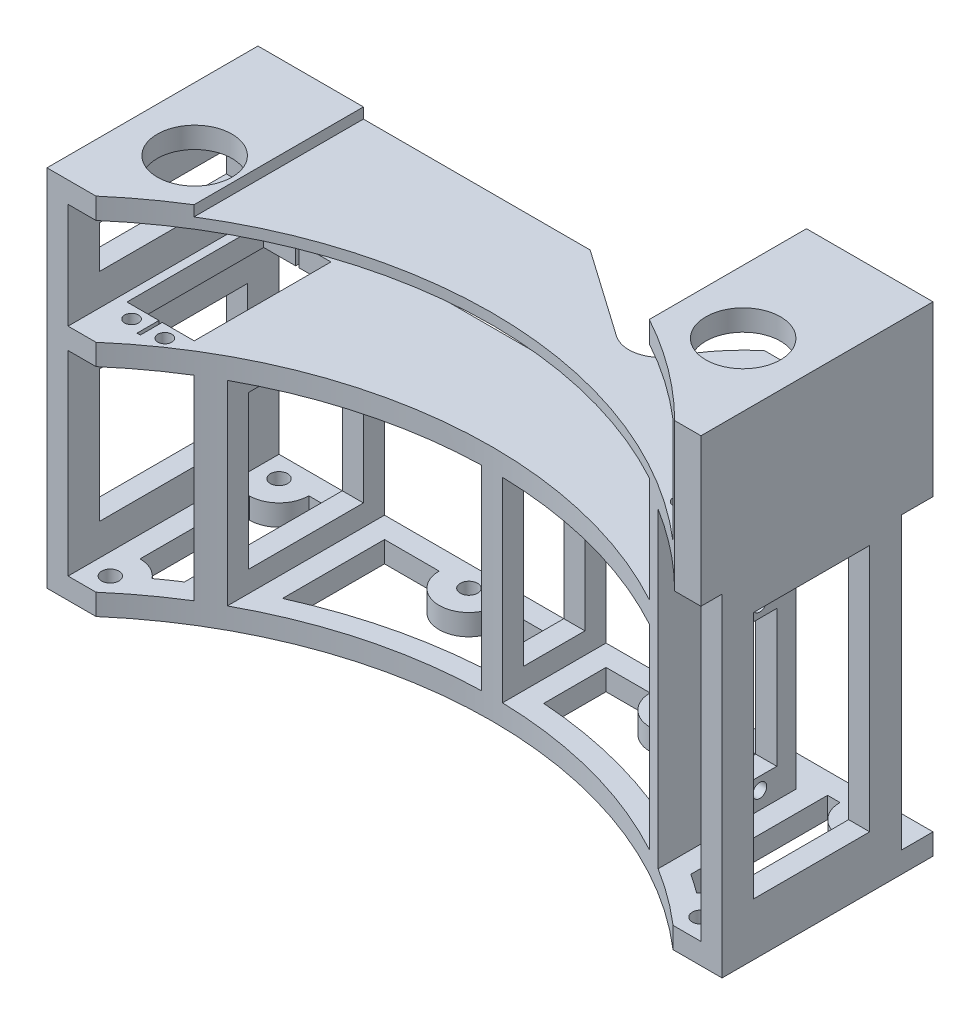
SolidWorks part; units mm, degrees
ref_plane "Front Plane" through (0, 0, 0) normal (0, 0, 1) x (1, 0, 0)
ref_plane "Top Plane" through (0, 0, 0) normal (0, 1, 0) x (1, 0, 0)
ref_plane "Right Plane" through (0, 0, 0) normal (1, 0, 0) x (0, 0, -1)
sketch "Sketch1" plane through (0, 0, 0) normal (0, 0, 1) x (1, 0, 0)
  line L0 (-101.6, 106.425) -> (101.6, 106.425)
  line L1 (-101.6, 0) -> (101.6, 0)
  line L2 (-101.6, 0) -> (-101.6, 106.425)
  line L4 (101.6, 0) -> (101.6, 106.425)
  point P5 (0, 0)
  dimension "D1" = 203.2
  dimension "D2" = 106.425
extrude "Boss-Extrude1" add sketch "Sketch1" along normal mid plane 63.5 contours L1 L4 L0 L2 | L0 region at (0, 53.2125, 0)
sketch "Sketch4" plane through (0, 0, -31.75) normal (0, 0, -1) x (-1, 0, 0)
  line L0 (-101.6, 0) -> (-101.6, 106.425) construction
  line L1 (101.6, 0) -> (101.6, 106.425) construction
  line L2 (-95.25, 103.25) -> (95.25, 103.25)
  line L3 (-95.25, 103.25) -> (-95.25, 71.5)
  line L4 (-95.25, 71.5) -> (95.25, 71.5)
  line L5 (95.25, 103.25) -> (95.25, 71.5)
  line L11 (-95.25, 65.15) -> (95.25, 65.15)
  line L12 (-95.25, 65.15) -> (-95.25, 6.35)
  line L13 (-95.25, 6.35) -> (95.25, 6.35)
  line L14 (95.25, 65.15) -> (95.25, 6.35)
  line L15 (101.6, 0) -> (-101.6, 0) construction
  dimension "D4" = 6.35
  dimension "D1" = 6.35
  dimension "D2" = 71.5
  dimension "D3" = 6.35
  dimension "D5" = 6.35
  dimension "D6" = 31.75
extrude "Cut-Extrude2" cut sketch "Sketch4" against normal through all
sketch "Sketch8" plane through (0, 0, 0) normal (0, 0, 1) x (1, 0, 0)
  line L0 (-95.25, 65.15) -> (95.25, 65.15) construction
  line L1 (-69.85, 65.15) -> (-63.5, 65.15)
  line L2 (-69.85, 65.15) -> (-69.85, 6.35)
  line L3 (-69.85, 6.35) -> (-63.5, 6.35)
  line L4 (-63.5, 65.15) -> (-63.5, 6.35)
  line L5 (95.25, 6.35) -> (-95.25, 6.35) construction
  line L6 (-95.25, 103.25) -> (95.25, 103.25) construction
  line L7 (63.5, 103.25) -> (69.85, 103.25)
  line L8 (63.5, 103.25) -> (63.5, 6.35)
  line L9 (63.5, 6.35) -> (69.85, 6.35)
  line L10 (69.85, 103.25) -> (69.85, 6.35)
  line L11 (95.25, 65.15) -> (95.25, 6.35) construction
  line L12 (-95.25, 6.35) -> (-95.25, 65.15) construction
  line L13 (-101.6, 0) -> (101.6, 0) construction
  line L14 (-3.175, 65.15) -> (3.175, 65.15)
  line L15 (-3.175, 65.15) -> (-3.175, 6.35)
  line L16 (-3.175, 6.35) -> (3.175, 6.35)
  line L17 (3.175, 65.15) -> (3.175, 6.35)
  point P24 (0, 0)
  point P25 (0, 6.35)
  dimension "D1" = 6.35
  dimension "D2" = 6.35
  dimension "D3" = 25.4
  dimension "D4" = 25.4
  dimension "D5" = 6.35
extrude "Boss-Extrude2" add sketch "Sketch8" along normal up to surface (31.75 mm away) from surface up to face at (0, 87.375, 31.75) starting at face at (0, 87.375, -31.75)
sketch "Sketch15" plane through (0, 103.25, 0) normal (0, -1, 0) x (1, 0, 0)
  line L4 (69.85, 31.75) -> (69.85, -31.75)
  line L5 (69.85, -31.75) -> (95.25, -31.75)
  line L6 (95.25, -31.75) -> (95.25, 31.75)
  line L7 (95.25, 31.75) -> (69.85, 31.75)
  line L8 (69.85, 31.75) -> (69.85, -31.75)
  line L9 (69.85, -31.75) -> (95.25, -31.75)
  line L10 (95.25, -31.75) -> (95.25, 31.75)
  line L11 (95.25, 31.75) -> (69.85, 31.75)
  dimension "D1" = 0
extrude "Boss-Extrude4" add sketch "Sketch15" along normal blind 3.175
sketch "Sketch2" plane through (0, 71.5, 0) normal (0, 1, 0) x (1, 0, 0)
  line L0 (-92.677, 24.55) -> (-72.423, -16.604) construction
  line L29 (-92.677, 24.55) -> (-83.05, 24.55)
  line L30 (-92.677, 24.55) -> (-92.677, -16.604)
  line L31 (-92.677, -16.604) -> (-83.05, -16.604)
  line L34 (-72.423, 24.55) -> (-72.423, -16.604)
  line L58 (69.85, 31.75) -> (69.85, -31.75)
  line L59 (69.85, -31.75) -> (95.25, -31.75)
  line L60 (95.25, -31.75) -> (95.25, 31.75)
  line L61 (95.25, 31.75) -> (69.85, 31.75)
  line L62 (69.85, 31.75) -> (69.85, -31.75)
  line L63 (69.85, -31.75) -> (95.25, -31.75)
  line L64 (95.25, -31.75) -> (95.25, 31.75)
  line L65 (95.25, 31.75) -> (69.85, 31.75)
  line L78 (-72.423, 24.55) -> (-92.677, -16.604) construction
  line L79 (-87.55, 28.273) -> (-77.55, -20.327) construction
  line L80 (-87.55, -20.327) -> (-77.55, 28.273) construction
  line L81 (-82.05, -16.604) -> (-72.423, -16.604)
  line L82 (-82.05, -16.604) -> (-82.05, -23.208)
  line L83 (-82.05, -23.208) -> (-83.05, -23.208)
  line L84 (-83.05, -16.604) -> (-83.05, -23.208)
  line L85 (-82.55, 3.973) -> (-13.3966, 3.973) construction
  line L86 (-82.05, 31.154) -> (-83.05, 31.154)
  line L87 (-82.05, 24.55) -> (-82.05, 31.154)
  line L88 (-83.05, 24.55) -> (-83.05, 31.154)
  line L89 (-82.05, 24.55) -> (-72.423, 24.55)
  line L90 (-101.6, -31.75) -> (101.6, -31.75) construction
  line L91 (-101.6, -31.75) -> (-101.6, 31.75) construction
  circle A12 centre (-87.55, -20.327) radius 2.1
  circle A13 centre (-77.55, -20.327) radius 2.1
  circle A14 centre (-87.55, 28.273) radius 2.1
  circle A15 centre (-77.55, 28.273) radius 2.1
  point P8 (-82.55, -23.208)
  point P17 (-82.55, 3.973)
  point P18 (-82.55, 3.973)
  point P27 (-82.55, -6.35)
  dimension "D3" = 48.6
  dimension "D4" = 4.2
  dimension "D2" = 10
  dimension "D5" = 41.154
  dimension "D6" = 20.254
  dimension "D7" = 1
  dimension "D8" = 6.604
  dimension "D9" = 30.9
  dimension "D10" = 25.4
  dimension "D11" = 0
  dimension "D12" = 19.05
extrude "Cut-Extrude3" cut sketch "Sketch2" against normal up to next
sketch "Sketch9" plane through (0, 106.425, 0) normal (0, 1, 0) x (1, 0, 0)
  line L0 (72.423, 24.55) -> (92.677, -16.604) construction
  line L1 (72.423, 24.55) -> (82.05, 24.55)
  line L2 (72.423, 24.55) -> (72.423, -16.604)
  line L3 (72.423, -16.604) -> (82.05, -16.604)
  line L4 (92.677, 24.55) -> (92.677, -16.604)
  line L5 (92.677, 24.55) -> (72.423, -16.604) construction
  line L6 (77.55, 28.273) -> (87.55, -20.327) construction
  line L7 (77.55, -20.327) -> (87.55, 28.273) construction
  line L8 (83.05, -16.604) -> (92.677, -16.604)
  line L9 (83.05, -16.604) -> (83.05, -23.208)
  line L10 (83.05, -23.208) -> (82.05, -23.208)
  line L11 (82.05, -16.604) -> (82.05, -23.208)
  line L12 (82.55, 3.973) -> (164.4034, 3.973) construction
  line L13 (83.05, 31.154) -> (82.05, 31.154)
  line L14 (83.05, 24.55) -> (83.05, 31.154)
  line L15 (82.05, 24.55) -> (82.05, 31.154)
  line L16 (83.05, 24.55) -> (92.677, 24.55)
  line L17 (101.6, -31.75) -> (101.6, 31.75) construction
  line L19 (-101.6, -31.75) -> (101.6, -31.75) construction
  circle A0 centre (77.55, -20.327) radius 2.1
  circle A1 centre (87.55, -20.327) radius 2.1
  circle A2 centre (77.55, 28.273) radius 2.1
  circle A3 centre (87.55, 28.273) radius 2.1
  point P8 (82.55, -23.208)
  point P17 (82.55, 3.973)
  point P18 (82.55, 3.973)
  point P27 (82.55, -6.35)
  dimension "D3" = 4.2
  dimension "D1" = 10
  dimension "D2" = 48.6
  dimension "D4" = 41.154
  dimension "D5" = 20.254
  dimension "D6" = 1
  dimension "D7" = 6.604
  dimension "D8" = 30.9
  dimension "D9" = 19.05
  dimension "D10" = 25.4
extrude "Cut-Extrude4" cut sketch "Sketch9" against normal up to next
sketch "Sketch12" plane through (0, 0, 0) normal (0, 1, 0) x (1, 0, 0)
  line L0 (-63.5, -31.75) -> (-63.5, 31.75) construction
  line L1 (-69.85, -31.75) -> (-95.25, -31.75) construction
  line L2 (-95.25, -31.75) -> (-95.25, 31.75) construction
  line L3 (-101.6, 31.75) -> (101.6, 31.75) construction
  circle A0 centre (-88.9, 25.4) radius 2.6
  circle A1 centre (-88.9, -25.4) radius 2.6
  circle A2 centre (-31.75, 25.4) radius 2.6
  dimension "D1" = 5.2
  dimension "D2" = 6.35
  dimension "D3" = 6.35
  dimension "D4" = 6.35
  dimension "D5" = 31.75
extrude "Cut-Extrude7" cut sketch "Sketch12" along normal up to surface (6.35 mm away) and the other way through all up to face at (-33.3375, 6.35, 0)
mirror "Mirror1" about plane through (0, 0, 0) normal (1, 0, 0) of "Cut-Extrude7"
sketch "Sketch16" plane through (0, 106.425, 0) normal (0, 1, 0) x (1, 0, 0)
  line L2 (-69.85, 31.75) -> (-101.6, 31.75)
  line L3 (-101.6, 31.75) -> (-101.6, -31.75)
  line L12 (-101.6, -31.75) -> (-69.85, -31.75)
  line L13 (-69.85, 31.75) -> (-69.85, -31.75)
  dimension "D1" = 31.75
extrude "Boss-Extrude5" add sketch "Sketch16" along normal blind 3.175
sketch "Sketch17" plane through (0, 109.6, 0) normal (0, 1, 0) x (1, 0, 0)
  line L0 (-101.6, -31.75) -> (-69.85, -31.75) construction
  line L1 (-101.6, 31.75) -> (-101.6, -31.75) construction
  circle A0 centre (-82.55, -6.35) radius 11.2395
  dimension "D3" = 22.479
  dimension "D1" = 25.4
  dimension "D2" = 19.05
extrude "Cut-Extrude8" cut sketch "Sketch17" against normal up to next
sketch "Sketch18" plane through (0, 106.425, 0) normal (0, 1, 0) x (1, 0, 0)
  line L5 (101.6, -31.75) -> (101.6, 31.75) construction
  line L6 (-69.85, -31.75) -> (101.6, -31.75) construction
  line L14 (101.6, -31.75) -> (101.6, 31.75)
  line L15 (101.6, 31.75) -> (95.25, 31.75)
  line L16 (95.25, -31.75) -> (95.25, 31.75)
  line L22 (95.25, -31.75) -> (82.55, -31.75)
  line L23 (101.6, -31.75) -> (101.6, -38.1)
  line L24 (101.6, -38.1) -> (82.55, -38.1)
  line L25 (82.55, -31.75) -> (82.55, -38.1)
  dimension "D4" = 6.35
  dimension "D5" = 19.05
extrude "Boss-Extrude6" add sketch "Sketch18" along normal blind 38.1 from surface starting at face at (87.55, 100.075, 18.227)
sketch "Sketch20" plane through (0, 138.175, 0) normal (0, 1, 0) x (1, 0, 0)
  line L1 (63.5, 31.75) -> (101.6, 31.75)
  line L2 (63.5, 31.75) -> (63.5, -38.1)
  line L3 (63.5, -38.1) -> (101.6, -38.1)
  line L4 (101.6, 31.75) -> (101.6, -38.1)
  line L6 (-69.85, -31.75) -> (82.55, -31.75) construction
  circle A0 centre (82.55, -6.35) radius 11.2395
  dimension "D2" = 19.05
  dimension "D1" = 22.479
  dimension "D4" = 38.1
  dimension "D3" = 25.4
extrude "Boss-Extrude7" add sketch "Sketch20" along normal blind 6.35
sketch "Sketch10" plane through (0, 106.425, 0) normal (0, 1, 0) x (1, 0, 0)
  circle A3 centre (0, -132.08) radius 131.1118 construction
  circle A4 centre (0, -132.08) radius 131.1118 construction
  circle A5 centre (0, -132.08) radius 132.6993
  dimension "D1" = 1.5875
extrude "Cut-Extrude5" cut sketch "Sketch10" against normal through all both and the other way through all
sketch "Sketch21" plane through (0, 106.425, 0) normal (0, 1, 0) x (1, 0, 0)
  line L5 (34.6759, 6.35) -> (-1.5991, 31.75)
  line L6 (-69.85, 31.75) -> (95.25, 31.75) construction
  line L7 (-1.5991, 31.75) -> (50.9018, 31.75)
  arc A1 (34.6759, 6.35) -> (50.9018, 31.75) centre (82.55, -6.35) cw
  dimension "D2" = 49.53
  dimension "D1" = 35
  dimension "D3" = 25.4
extrude "Cut-Extrude10" cut sketch "Sketch21" against normal up to surface (3.175 mm away) up to face at (-82.55, 103.25, 17.5895)
sketch "Sketch32" plane through (0, 6.35, 0) normal (0, 1, 0) x (1, 0, 0)
  line L8 (76.2, 25.4) -> (76.2, -15.769)
  line L9 (88.9, -25.1619) -> (88.9, 25.4)
  line L10 (88.9, 25.4) -> (76.2, 25.4)
  line L11 (76.2, 25.4) -> (76.2, -15.769)
  line L12 (88.9, -16.45) -> (88.9, 16.45)
  line L13 (79.95, 25.4) -> (76.2, 25.4)
  line L32 (-57.15, 25.4) -> (-57.15, -5.3181)
  line L33 (-9.525, 6.6426) -> (-9.525, 25.4)
  line L40 (-76.2, -15.769) -> (-76.2, 25.4)
  line L41 (-76.2, 25.4) -> (-88.9, 25.4)
  line L42 (-88.9, 25.4) -> (-88.9, -25.1619)
  line L43 (-76.2, -15.769) -> (-76.2, 25.4)
  line L44 (-76.2, 25.4) -> (-79.95, 25.4)
  line L45 (-88.9, 16.45) -> (-88.9, -16.45)
  line L48 (-9.525, 25.4) -> (-57.15, 25.4)
  line L49 (-57.15, 25.4) -> (-57.15, -5.3181)
  line L50 (-9.525, 6.6426) -> (-9.525, 25.4)
  line L67 (-9.525, 25.4) -> (-22.8, 25.4)
  line L68 (-40.7, 25.4) -> (-57.15, 25.4)
  line L69 (22.8, 25.4) -> (9.525, 25.4)
  line L71 (9.525, 25.4) -> (9.525, 6.6426)
  line L72 (57.15, -5.3181) -> (57.15, 25.4)
  line L73 (57.15, 25.4) -> (9.525, 25.4)
  line L74 (9.525, 25.4) -> (9.525, 6.6426)
  line L75 (57.15, -5.3181) -> (57.15, 25.4)
  line L76 (57.15, 25.4) -> (40.7, 25.4)
  circle A2 centre (88.9, 25.4) radius 8.95
  arc A3 (79.95, 25.4) -> (88.9, 16.45) centre (88.9, 25.4) ccw
  arc A8 (88.9, -25.1619) -> (76.2, -15.769) centre (0, -132.08) ccw
  circle A9 centre (88.9, -25.4) radius 8.95
  arc A10 (88.9, -16.45) -> (81.9575, -19.7516) centre (88.9, -25.4) ccw
  arc A11 (81.9575, -19.7516) -> (76.2, -15.769) centre (0, -132.08) ccw
  circle A13 centre (-31.75, 25.4) radius 8.95
  arc A22 (-76.2, -15.769) -> (-88.9, -25.1619) centre (0, -132.08) ccw
  arc A23 (-76.2, -15.769) -> (-81.9575, -19.7516) centre (0, -132.08) ccw
  arc A26 (-40.7, 25.4) -> (-22.8, 25.4) centre (-31.75, 25.4) ccw
  circle A27 centre (-88.9, 25.4) radius 8.95
  arc A28 (-88.9, 16.45) -> (-79.95, 25.4) centre (-88.9, 25.4) ccw
  circle A30 centre (-88.9, -25.4) radius 8.95
  arc A31 (-81.9575, -19.7516) -> (-88.9, -16.45) centre (-88.9, -25.4) ccw
  circle A33 centre (31.75, 25.4) radius 8.95
  arc A35 (22.8, 25.4) -> (40.7, 25.4) centre (31.75, 25.4) ccw
  arc A38 (-9.525, 6.6426) -> (-57.15, -5.3181) centre (0, -132.08) ccw
  arc A39 (-9.525, 6.6426) -> (-57.15, -5.3181) centre (0, -132.08) ccw
  arc A42 (57.15, -5.3181) -> (9.525, 6.6426) centre (0, -132.08) ccw
  arc A43 (57.15, -5.3181) -> (9.525, 6.6426) centre (0, -132.08) ccw
  dimension "D1" = 6.35
  dimension "D2" = 6.35
  dimension "D3" = 6.35
  dimension "D4" = 6.35
  dimension "D5" = 6.35
  dimension "D6" = 6.35
  dimension "D7" = 6.35
  dimension "D8" = 6.35
  dimension "D9" = 6.35
  dimension "D10" = 6.35
extrude "Cut-Extrude19" cut sketch "Sketch32" against normal up to next
sketch "Sketch23" plane through (0, 0, -31.75) normal (0, 0, -1) x (-1, 0, 0)
  line L1 (-101.6, 6.35) -> (-57.15, 6.35)
  line L2 (-101.6, 6.35) -> (-101.6, 93.725)
  line L3 (-101.6, 93.725) -> (-57.15, 93.725)
  line L4 (-57.15, 6.35) -> (-57.15, 93.725)
  line L7 (-63.5, 71.5) -> (95.25, 71.5) construction
  line L9 (-63.5, 65.15) -> (-63.5, 6.35) construction
  line L10 (-101.6, 0) -> (-101.6, 144.525) construction
  line L11 (-63.5, 6.35) -> (-3.175, 6.35) construction
  dimension "D1" = 6.35
  dimension "D2" = 22.225
extrude "Cut-Extrude11" cut sketch "Sketch23" against normal blind 9.525
sketch "Sketch24" plane through (63.5, 0, 0) normal (-1, 0, 0) x (0, 0, 1)
  line L0 (-16.477, 56.354) -> (3.777, 15.2) construction
  line L1 (-16.477, 56.354) -> (-6.85, 56.354)
  line L2 (-16.477, 56.354) -> (-16.477, 15.2)
  line L3 (-16.477, 15.2) -> (-6.85, 15.2)
  line L4 (3.777, 56.354) -> (3.777, 15.2)
  line L5 (3.777, 56.354) -> (-16.477, 15.2) construction
  line L6 (-11.35, 60.077) -> (-1.35, 11.477) construction
  line L7 (-11.35, 11.477) -> (-1.35, 60.077) construction
  line L8 (-5.85, 15.2) -> (3.777, 15.2)
  line L9 (-5.85, 15.2) -> (-5.85, 8.596)
  line L10 (-5.85, 8.596) -> (-6.85, 8.596)
  line L11 (-6.85, 15.2) -> (-6.85, 8.596)
  line L12 (-6.35, 35.777) -> (65.4757, 35.777) construction
  line L13 (-5.85, 62.958) -> (-6.85, 62.958)
  line L14 (-5.85, 56.354) -> (-5.85, 62.958)
  line L15 (-6.85, 56.354) -> (-6.85, 62.958)
  line L16 (-5.85, 56.354) -> (3.777, 56.354)
  line L17 (-22.225, 65.15) -> (-22.225, 6.35) construction
  line L18 (15.5603, 65.15) -> (-22.225, 65.15) construction
  circle A0 centre (-11.35, 11.477) radius 2.1
  circle A1 centre (-1.35, 11.477) radius 2.1
  circle A2 centre (-11.35, 60.077) radius 2.1
  circle A3 centre (-1.35, 60.077) radius 2.1
  point P8 (-6.35, 8.596)
  point P17 (-6.35, 35.777)
  point P18 (-6.35, 35.777)
  point P27 (-6.35, 46.1)
  dimension "D3" = 4.2
  dimension "D1" = 10
  dimension "D2" = 48.6
  dimension "D4" = 41.154
  dimension "D5" = 20.254
  dimension "D6" = 1
  dimension "D7" = 6.604
  dimension "D8" = 30.9
  dimension "D9" = 15.875
  dimension "D10" = 19.05
extrude "Cut-Extrude12" cut sketch "Sketch24" against normal up to next
sketch "Sketch26" plane through (95.25, 0, 0) normal (-1, 0, 0) x (0, 0, 1)
  line L12 (-12.7, 90.55) -> (-12.7, 15.875)
  line L13 (-12.7, 15.875) -> (22.225, 15.875)
  line L14 (22.225, 15.875) -> (22.225, 90.55)
  line L15 (22.225, 90.55) -> (-12.7, 90.55)
  line L16 (-12.7, 90.55) -> (-12.7, 15.875)
  line L17 (-12.7, 15.875) -> (22.225, 15.875)
  line L18 (22.225, 15.875) -> (22.225, 90.55)
  line L19 (22.225, 90.55) -> (-12.7, 90.55)
  dimension "D1" = 9.525
extrude "Cut-Extrude13" cut sketch "Sketch26" against normal up to next
sketch "Sketch27" plane through (63.5, 0, 0) normal (-1, 0, 0) x (0, 0, 1)
  line L12 (-15.875, 96.9) -> (-15.875, 77.85)
  line L13 (-15.875, 77.85) -> (9.2103, 77.85)
  line L14 (9.2103, 77.85) -> (9.2103, 96.9)
  line L15 (9.2103, 96.9) -> (-15.875, 96.9)
  line L16 (-15.875, 96.9) -> (-15.875, 77.85)
  line L17 (-15.875, 77.85) -> (9.2103, 77.85)
  line L18 (9.2103, 77.85) -> (9.2103, 96.9)
  line L19 (9.2103, 96.9) -> (-15.875, 96.9)
  dimension "D1" = 6.35
extrude "Cut-Extrude14" cut sketch "Sketch27" against normal up to next
sketch "Sketch28" plane through (3.175, 0, 0) normal (1, 0, 0) x (0, 0, -1)
  line L8 (25.4, 58.8) -> (6.9313, 58.8)
  line L9 (6.9313, 58.8) -> (6.9313, 12.7)
  line L10 (6.9313, 12.7) -> (25.4, 12.7)
  line L11 (25.4, 12.7) -> (25.4, 58.8)
  line L12 (25.4, 58.8) -> (6.9313, 58.8)
  line L13 (6.9313, 58.8) -> (6.9313, 12.7)
  line L14 (6.9313, 12.7) -> (25.4, 12.7)
  line L15 (25.4, 12.7) -> (25.4, 58.8)
  dimension "D1" = 6.35
extrude "Cut-Extrude15" cut sketch "Sketch28" against normal up to next
sketch "Sketch29" plane through (-63.5, 0, 0) normal (1, 0, 0) x (0, 0, -1)
  line L8 (25.4, 58.8) -> (-9.2103, 58.8)
  line L9 (-9.2103, 58.8) -> (-9.2103, 12.7)
  line L10 (-9.2103, 12.7) -> (25.4, 12.7)
  line L11 (25.4, 12.7) -> (25.4, 58.8)
  line L12 (25.4, 58.8) -> (-9.2103, 58.8)
  line L13 (-9.2103, 58.8) -> (-9.2103, 12.7)
  line L14 (-9.2103, 12.7) -> (25.4, 12.7)
  line L15 (25.4, 12.7) -> (25.4, 58.8)
  dimension "D1" = 6.35
extrude "Cut-Extrude16" cut sketch "Sketch29" against normal up to next
sketch "Sketch30" plane through (-95.25, 0, 0) normal (1, 0, 0) x (0, 0, -1)
  line L8 (22.225, 15.875) -> (22.225, 55.625)
  line L9 (22.225, 55.625) -> (-22.225, 55.625)
  line L10 (-22.225, 55.625) -> (-22.225, 15.875)
  line L11 (-22.225, 15.875) -> (22.225, 15.875)
  line L12 (22.225, 15.875) -> (22.225, 55.625)
  line L13 (22.225, 55.625) -> (-22.225, 55.625)
  line L14 (-22.225, 55.625) -> (-22.225, 15.875)
  line L15 (-22.225, 15.875) -> (22.225, 15.875)
  dimension "D1" = 9.525
extrude "Cut-Extrude17" cut sketch "Sketch30" against normal up to next
sketch "Sketch31" plane through (-95.25, 0, 0) normal (1, 0, 0) x (0, 0, -1)
  line L4 (22.225, 81.025) -> (22.225, 93.725)
  line L6 (22.225, 81.025) -> (22.225, 93.725)
  line L9 (22.225, 93.725) -> (-22.225, 93.725)
  line L10 (-22.225, 93.725) -> (-22.225, 81.025)
  line L11 (-22.225, 81.025) -> (22.225, 81.025)
  line L13 (22.225, 93.725) -> (-22.225, 93.725)
  line L14 (-22.225, 93.725) -> (-22.225, 81.025)
  line L15 (-22.225, 81.025) -> (22.225, 81.025)
  dimension "D1" = 9.525
extrude "Cut-Extrude18" cut sketch "Sketch31" against normal up to next
fillet "Fillet1" radius 9.525 1 edges at (34.6759, 104.8375, -6.35)
equation "\"tightTol\"= 0.005in"
equation "\"normTol\"= 0.01in"
equation "\"looseTol\"= 0.02in"
equation "\"D1@Sketch12\"=5.2mm"
equation "\"D2@Sketch1\"=8mm+0.5+3.25+0.125"
equation "\"D2@Sketch4\"=8mm+0.25+2.25"
equation "\"D3@Sketch17\" = 7 / 8 + \"normTol\""
equation "\"D1@Sketch20\"=7/8+\"normTol\""
